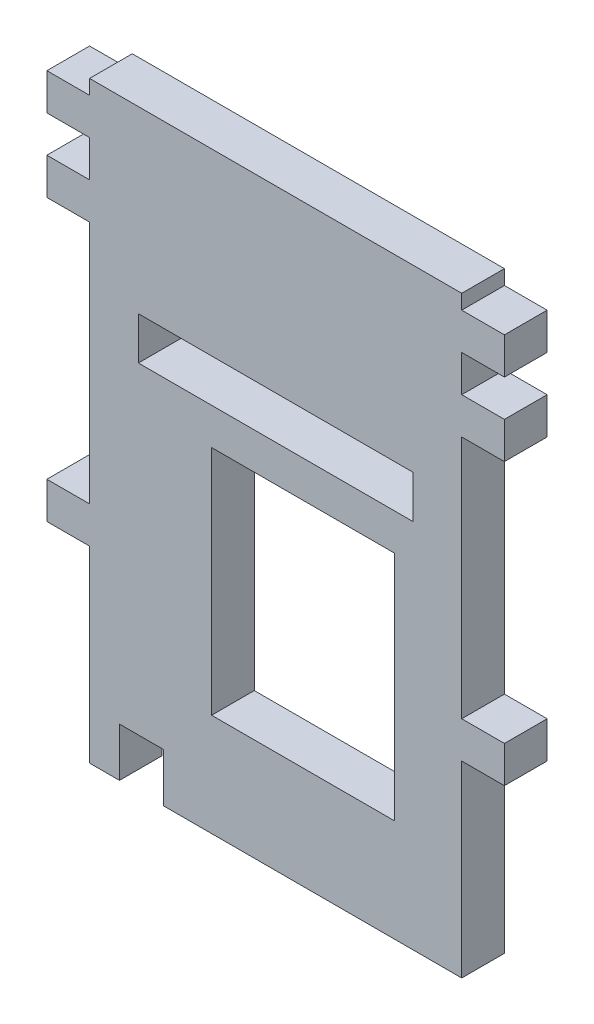
SolidWorks part; units mm, degrees
ref_plane "Ebene vorne (XY)" through (0, 0, 0) normal (0, 0, 1) x (1, 0, 0)
ref_plane "Ebene oben  (XZ)" through (0, 0, 0) normal (0, 1, 0) x (1, 0, 0)
ref_plane "Ebene rechts  (YZ)" through (0, 0, 0) normal (1, 0, 0) x (0, 0, -1)
ref_axis "x-Achse" through (-5.375, 0, 0) along (1, 0, 0)
ref_axis "y-Achse" through (0, 8.63, 0) along (0, -1, 0)
ref_axis "z-Achse" through (0, 0, -0.175) along (0, 0, 1)
sketch "Profile_Laser_profile_3p5" plane through (0, 0, 0) normal (0, 0, 1) x (1, 0, 0)
  line L0 (0, -42.4) -> (2.45, -42.4)
  line L1 (2.45, -42.4) -> (2.45, -38.401)
  line L2 (2.45, -38.401) -> (6.05, -38.401)
  line L3 (6.05, -38.401) -> (6.05, -42.4)
  line L4 (6.05, -42.4) -> (30.5, -42.4)
  line L5 (30.5, -42.4) -> (30.5, -27)
  line L6 (30.5, -27) -> (34, -27)
  line L7 (34, -27) -> (34, -24)
  line L8 (34, -24) -> (30.5, -24)
  line L9 (30.5, -24) -> (30.5, -4)
  line L10 (30.5, -4) -> (34, -4)
  line L11 (34, -4) -> (34, -1)
  line L12 (34, -1) -> (30.5, -1)
  line L13 (30.5, -1) -> (30.5, 2)
  line L14 (30.5, 2) -> (34, 2)
  line L15 (34, 2) -> (34, 5)
  line L16 (34, 5) -> (30.5, 5)
  line L17 (30.5, 5) -> (30.5, 6.2)
  line L18 (30.5, 6.2) -> (0, 6.2)
  line L19 (0, 6.2) -> (0, 5)
  line L20 (0, 5) -> (-3.5, 5)
  line L21 (-3.5, 5) -> (-3.5, 2)
  line L22 (-3.5, 2) -> (0, 2)
  line L23 (0, 2) -> (0, -1)
  line L24 (0, -1) -> (-3.5, -1)
  line L25 (-3.5, -1) -> (-3.5, -4)
  line L26 (-3.5, -4) -> (0, -4)
  line L27 (0, -4) -> (0, -24)
  line L28 (0, -24) -> (-3.5, -24)
  line L29 (-3.5, -24) -> (-3.5, -27)
  line L30 (-3.5, -27) -> (0, -27)
  line L31 (0, -27) -> (0, -42.4)
  line L32 (4, -12) -> (26.5, -12)
  line L33 (26.5, -12) -> (26.5, -8.5)
  line L34 (26.5, -8.5) -> (4, -8.5)
  line L35 (4, -8.5) -> (4, -12)
  line L36 (10, -34) -> (25, -34)
  line L37 (25, -34) -> (25, -15)
  line L38 (25, -15) -> (10, -15)
  line L39 (10, -15) -> (10, -34)
extrude "Laser_profile_3p5" add sketch "Profile_Laser_profile_3p5" along normal blind 3.5
